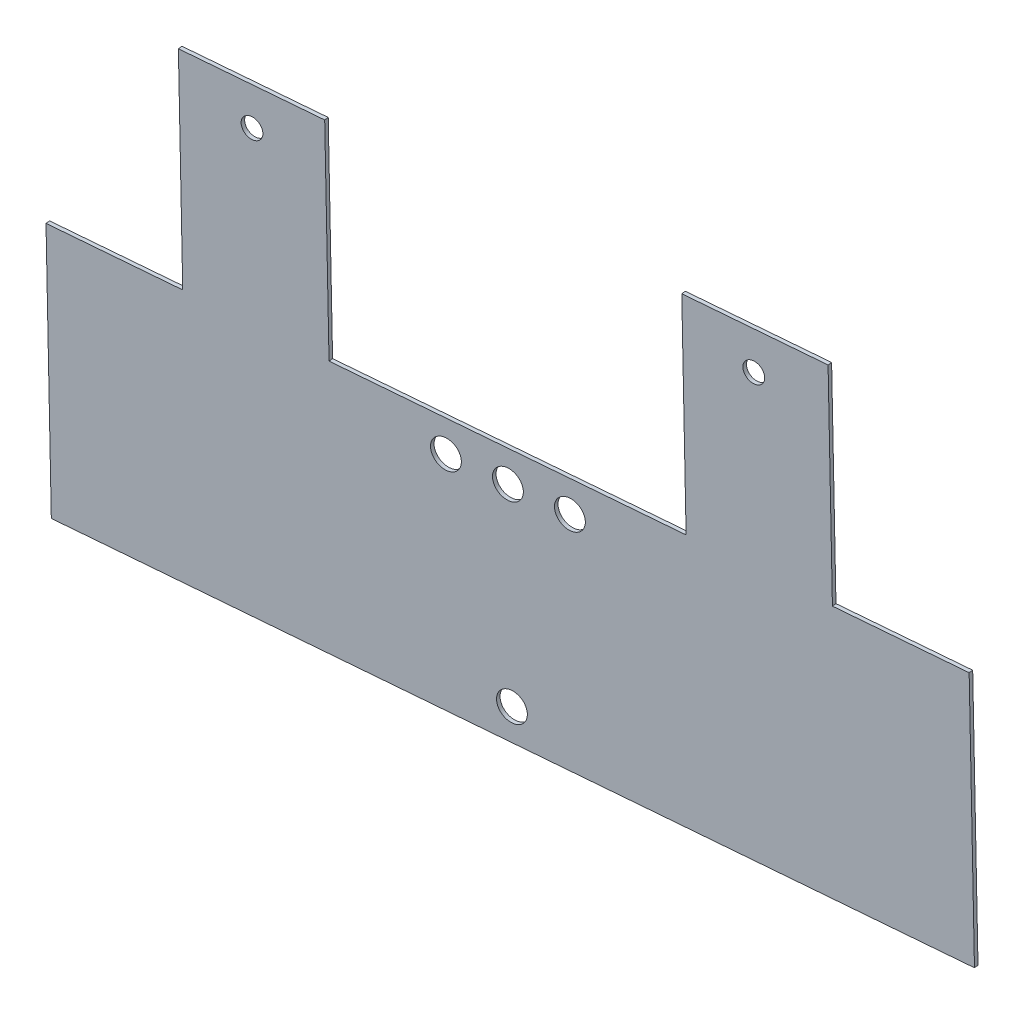
SolidWorks part; units mm, degrees
ref_plane "Front Plane" through (0, 0, 0) normal (0, 0, 1) x (1, 0, 0)
ref_plane "Top Plane" through (0, 0, 0) normal (0, 1, 0) x (1, 0, 0)
ref_plane "Right Plane" through (0, 0, 0) normal (1, 0, 0) x (0, 0, -1)
sketch "Sketch1" plane through (16.9972, -4.1499, 204.6314) normal (-0.0828, 0.0202, -0.9964) x (0.9966, 0.002, -0.0827)
  line L0 (-405.6316, 283.217) -> (-385.6926, 283.217)
  line L1 (-520.3126, 323.857) -> (-500.3736, 323.857)
  line L2 (-520.3126, 323.857) -> (-520.3126, 283.217)
  line L3 (-520.3126, 283.217) -> (-500.3736, 283.217)
  line L4 (-385.6926, 323.857) -> (-385.6926, 283.217)
  line L6 (-426.9676, 283.217) -> (-426.9676, 250.0037)
  line L7 (-426.9676, 250.0037) -> (-405.6316, 250.0037)
  line L8 (-405.6316, 283.217) -> (-405.6316, 250.0037)
  line L9 (-405.0144, 323.857) -> (-385.6926, 323.857)
  line L14 (-479.4985, 323.857) -> (-465.3599, 323.857)
  line L20 (-500.3736, 283.217) -> (-500.3736, 250.0037)
  line L21 (-500.3736, 250.0037) -> (-479.0376, 250.0037)
  line L22 (-479.0376, 283.217) -> (-479.0376, 250.0037)
  line L23 (-479.0376, 283.217) -> (-426.9676, 283.217)
  line L24 (-432.4144, 323.857) -> (-405.0144, 323.857)
  line L25 (-500.3736, 323.857) -> (-479.4985, 323.857)
  line L26 (-445.0971, 323.857) -> (-432.4144, 323.857)
  line L31 (-465.3599, 323.857) -> (-445.0971, 323.857)
  dimension "D1" = 134.62
  dimension "D2" = 40.64
  dimension "D3" = 21.336
  dimension "D4" = 52.07
  dimension "D5" = 33.2133
extrude "Boss-Extrude1" add sketch "Sketch1" along normal blind 0.6096
ref_plane "Plane1" through (-508.5923, -1, 42.2247) normal (0.9966, 0.002, -0.0827) x (-0.0828, 0.028, -0.9962)
sketch "Sketch5" plane through (16.9468, -4.1376, 204.024) normal (-0.0828, 0.0202, -0.9964) x (-0.9966, -0.0017, 0.0827)
  circle A1 centre (452.9566, -318.9845) radius 2.25
extrude "Cut-Extrude2" cut sketch "Sketch5" against normal up to surface (0.6096 mm away) up to face at (-434.373, -283.8993, 236.4501)
ref_plane "Plane2" through (0.0852, -303.4744, -6.1615) normal (0.0003, -0.9998, -0.0203) x (-1, -0.0003, 0)
mirror "Mirror1" about plane through (0.0852, -303.4744, -6.1615) normal (0.0003, -0.9998, -0.0203) of "Cut-Extrude2"
sketch "Sketch6" plane through (16.9468, -4.1376, 204.024) normal (-0.0828, 0.0202, -0.9964) x (-0.9966, -0.0017, 0.0827)
  circle A1 centre (416.5068, -256.1738) radius 1.5875
  dimension "D1" = 3.175
  dimension "D2" = 103.726
  dimension "D3" = 6.0353
extrude "Cut-Extrude5" cut sketch "Sketch6" against normal up to surface (0.6096 mm away) up to face at (-436.6564, -293.1953, 236.4512)
ref_plane "Plane3" through (-451.4485, -0.8877, 37.4805) normal (-0.9966, -0.002, 0.0827) x (0.0827, 0.0002, 0.9966)
sketch "Sketch7" plane through (16.9468, -4.1376, 204.024) normal (-0.0828, 0.0202, -0.9964) x (-0.9966, -0.0017, 0.0827)
  circle A0 centre (489.6815, -256.1944) radius 1.5875
  dimension "D1" = 3.175
  dimension "D2" = 10.7236
  dimension "D3" = 6.0559
extrude "Cut-Extrude6" cut sketch "Sketch7" against normal up to surface (0.6096 mm away) up to face at (-399.6628, -260.97, 234.0319)
sketch "Sketch8" plane through (16.9972, -4.1499, 204.6314) normal (0.0828, -0.0202, 0.9964) x (0.9966, 0.0017, -0.0827)
  circle A0 centre (-443.9257, -288.342) radius 2.25
  circle A1 centre (-960.2704, 120.8255) radius 2.25
  circle A2 centre (-462.0048, -288.3471) radius 2.25
  point P6 (-462.9262, -288.2522)
  point P7 (-461.5639, -288.0698)
  point P8 (0, 0)
  point P9 (-462.0048, -288.3471)
  point P10 (-443.9257, -288.342)
extrude "Cut-Extrude7" cut sketch "Sketch8" against normal blind 2.54
